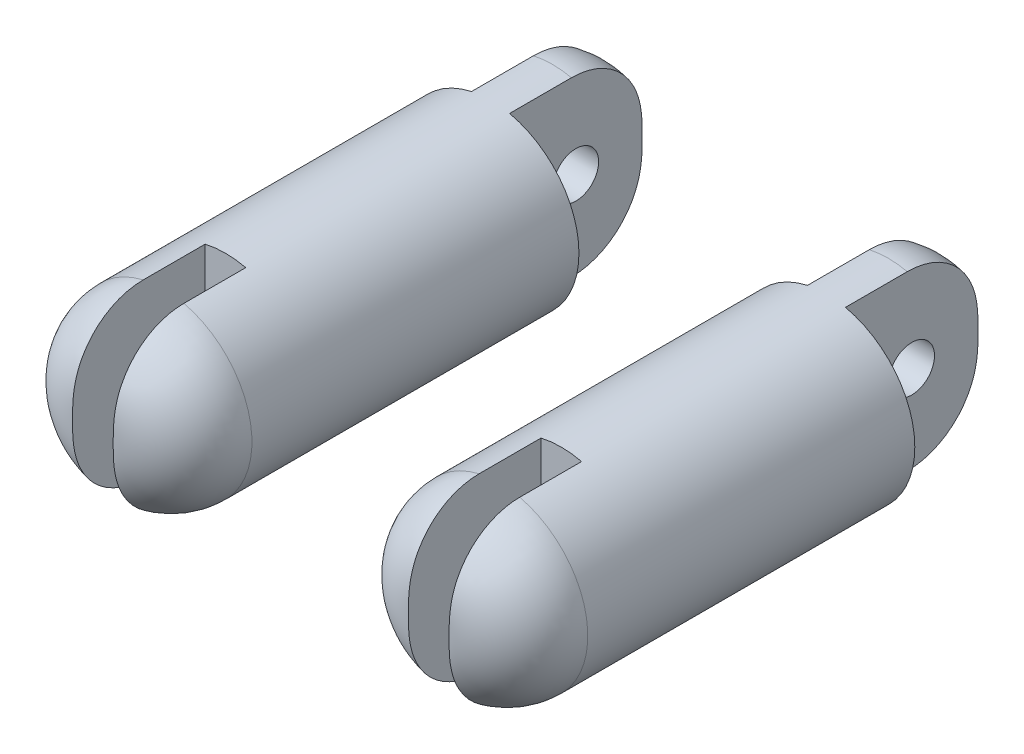
SolidWorks part; units mm, degrees
ref_plane "Front Plane" through (0, 0, 0) normal (0, 0, 1) x (1, 0, 0)
ref_plane "Top Plane" through (0, 0, 0) normal (0, 1, 0) x (1, 0, 0)
ref_plane "Right Plane" through (0, 0, 0) normal (1, 0, 0) x (0, 0, -1)
sketch "Sketch1" plane through (0, 0, 0) normal (0, 0, 1) x (1, 0, 0)
  circle A0 centre (147.5676, 0) radius 100
  circle A1 centre (-232.4324, 0) radius 100
  dimension "D1" = 200
  dimension "D2" = 200
  dimension "D3" = 380
extrude "Boss-Extrude1" add sketch "Sketch1" along normal blind 600
fillet "Fillet1" radius 80 1 edges at (-132.4324, 0, 600)
fillet "Fillet2" radius 80 1 edges at (247.5676, 0, 600)
ref_plane "Plane1" through (0, 0, 600) normal (0, 0, 1) x (1, 0, 0)
sketch "Sketch2" plane through (0, 0, 600) normal (0, 0, 1) x (1, 0, 0)
  line L0 (-232.4324, 100) -> (-232.4324, -100) construction
  line L2 (-255.4324, -115.931) -> (-209.4324, -115.931)
  line L3 (-255.4324, -115.931) -> (-255.4324, 115.931)
  line L4 (-255.4324, 115.931) -> (-209.4324, 115.931)
  line L5 (-209.4324, -115.931) -> (-209.4324, 115.931)
  line L6 (-255.4324, -115.931) -> (-209.4324, 115.931) construction
  line L7 (-255.4324, 115.931) -> (-209.4324, -115.931) construction
  line L8 (124.5676, -115.931) -> (170.5676, -115.931)
  line L9 (124.5676, -115.931) -> (124.5676, 115.931)
  line L10 (124.5676, 115.931) -> (170.5676, 115.931)
  line L11 (170.5676, -115.931) -> (170.5676, 115.931)
  line L12 (124.5676, -115.931) -> (170.5676, 115.931) construction
  line L13 (124.5676, 115.931) -> (170.5676, -115.931) construction
  circle A0 centre (-232.4324, 0) radius 100 construction
  point P4 (-232.4324, 0)
  point P9 (147.5676, 0)
  dimension "D1" = 46
  dimension "D2" = 46
extrude "Cut-Extrude1" cut sketch "Sketch2" against normal blind 150
ref_plane "Plane2" through (-132.4324, 0, 0) normal (1, 0, 0) x (0, 0, -1)
ref_plane "Plane3" through (-332.4324, 0, 0) normal (-1, 0, 0) x (0, 0, 1)
ref_plane "Plane4" through (-232.4324, 0, 0) normal (-1, 0, 0) x (0, 0, 1)
sketch "Sketch3" plane through (-232.4324, 0, 0) normal (1, 0, 0) x (0, 0, -1)
  line L0 (-599.9437, 0) -> (-449.9585, 0) construction
  circle A0 centre (-524.9511, 0) radius 20.1551
  spline S0 degree 3 poles (-520, -97.3191) (-521.4805, -97.3191) (-522.9639, -97.2769) (-525.1936, -97.1492) (-525.9376, -97.0959) (-527.427, -96.9676) (-528.1733, -96.8925) (-531.8854, -96.4646) (-534.8091, -95.9549) (-540.5675, -94.6119) (-543.4022, -93.7785) (-547.5872, -92.2845) (-548.971, -91.7458) (-551.0296, -90.8755) (-551.7129, -90.575) (-553.0738, -89.9531) (-553.751, -89.6318) (-557.1007, -87.9831) (-559.6824, -86.5222) (-564.6562, -83.3259) (-567.0482, -81.5904) (-570.4934, -78.7805) (-571.6179, -77.8093) (-573.8185, -75.7968) (-574.8973, -74.7523) (-578.024, -71.5486) (-579.9713, -69.3121) (-583.6015, -64.6453) (-585.2844, -62.215) (-587.6111, -58.4244) (-588.3537, -57.1367) (-589.7723, -54.5124) (-590.4495, -53.1729) (-593.6321, -46.4282) (-595.559, -40.8337) (-597.2787, -33.6194) (-597.5881, -32.1655) (-598.1409, -29.2364) (-598.3844, -27.759) (-599.0179, -23.3262) (-599.3114, -20.3634) (-599.7094, -14.4269) (-599.8145, -11.4531) (-599.9017, -6.9883) (-599.9192, -5.4993) (-599.9353, -3.2653) (-599.9389, -2.5205) (-599.9433, -1.0308) (-599.9441, -0.2845) (-599.9413, 3.4235) (-599.9216, 6.3892) (-599.7866, 12.3168) (-599.6678, 15.2785) (-599.3433, 19.7151) (-599.2109, 21.193) (-598.8885, 24.1464) (-598.6989, 25.6171) (-598.038, 30) (-597.4735, 32.8866) (-595.3686, 41.4291) (-593.4197, 46.9685) (-590.5235, 52.9997) (-590.1915, 53.6678) (-589.5119, 54.9896) (-588.4681, 56.9536) (-587.3514, 58.862) (-585.0218, 62.6054) (-583.3409, 65.0034) (-579.7234, 69.6043) (-577.787, 71.8073) (-574.6846, 74.961) (-573.6174, 75.987) (-571.9657, 77.4871) (-571.4061, 77.9811) (-570.2775, 78.9492) (-569.7076, 79.4241) (-566.8303, 81.7542) (-562.05, 85.196) (-556.9236, 88.077) (-552.9468, 90.0239) (-551.5991, 90.6372) (-549.5438, 91.5022) (-548.8519, 91.7819) (-547.464, 92.3198) (-546.7678, 92.5782) (-543.2757, 93.8183) (-537.6172, 95.4702) (-531.82, 96.4733) (-527.4194, 96.9788) (-525.9437, 97.1061) (-523.7166, 97.2339) (-522.9709, 97.2659) (-521.4834, 97.3085) (-520.741, 97.3191) (-520, 97.3191) knots 0 0 0 0 0.015625 0.015625 0.023437 0.023437 0.03125 0.03125 0.0625 0.0625 0.09375 0.09375 0.109375 0.109375 0.117187 0.117187 0.125 0.125 0.15625 0.15625 0.1875 0.1875 0.203125 0.203125 0.21875 0.21875 0.25 0.25 0.28125 0.28125 0.296875 0.296875 0.3125 0.3125 0.375 0.375 0.390625 0.390625 0.40625 0.40625 0.4375 0.4375 0.46875 0.46875 0.484375 0.484375 0.492187 0.492187 0.5 0.5 0.53125 0.53125 0.5625 0.5625 0.578125 0.578125 0.59375 0.59375 0.625 0.625 0.6875 0.6875 0.695312 0.695312 0.703125 0.71875 0.71875 0.75 0.75 0.78125 0.78125 0.796875 0.796875 0.804687 0.804687 0.8125 0.8125 0.84375 0.875 0.875 0.890625 0.890625 0.898438 0.898438 0.90625 0.90625 0.9375 0.96875 0.96875 0.984375 0.984375 0.992188 0.992188 1 1 1 1 construction
  point P3 (-448.2608, 0)
  point P6 (0, 0)
  point P7 (-610.9524, 0)
  point P8 (0, 0)
  point P9 (-599.9437, 0)
  point P12 (-449.9585, 0)
extrude "Boss-Extrude2" add sketch "Sketch3" along normal up to surface and the other way up to surface up to face at (-209.4324, 0.5625, 465.0151) other way up to face at (-255.4324, -0.5625, 465.0151)
sketch "Sketch4" plane through (0, 0, 0) normal (0, 0, -1) x (-1, 0, 0)
  line L1 (-169.0819, -97.6583) -> (-126.0533, -97.6583)
  line L2 (-169.0819, -97.6583) -> (-169.0819, 97.6583)
  line L3 (-169.0819, 97.6583) -> (-126.0533, 97.6583)
  line L4 (-126.0533, -97.6583) -> (-126.0533, 97.6583)
  line L5 (-169.0819, -97.6583) -> (-126.0533, 97.6583) construction
  line L6 (-169.0819, 97.6583) -> (-126.0533, -97.6583) construction
  line L7 (210.9181, -97.6583) -> (253.9467, -97.6583)
  line L8 (210.9181, -97.6583) -> (210.9181, 97.6583)
  line L9 (210.9181, 97.6583) -> (253.9467, 97.6583)
  line L10 (253.9467, -97.6583) -> (253.9467, 97.6583)
  line L11 (210.9181, -97.6583) -> (253.9467, 97.6583) construction
  line L12 (210.9181, 97.6583) -> (253.9467, -97.6583) construction
  circle A0 centre (-147.5676, 0) radius 100 construction
  circle A1 centre (232.4324, 0) radius 100 construction
  circle A2 centre (-147.5676, 0) radius 100
  circle A3 centre (232.4324, 0) radius 100
  point P0 (-147.5676, 0)
  point P8 (232.4324, 0)
  circle M1 centre (-147.5676, 0) radius 100
extrude "Cut-Extrude2" cut sketch "Sketch4" against normal blind 150 contours L10 A3 | L8 A3 | L4 M1 | L2 M1 region at (201.8508, 0, 0) region at (93.2844, 0, 0) region at (-178.1492, 0, 0) region at (-286.7156, 0, 0)
fillet "Fillet3" radius 80 1 edges at (147.5676, 100, 0)
fillet "Fillet4" radius 80 1 edges at (-232.4324, 100, 0)
sketch "Sketch5" plane through (169.0819, 0, 0) normal (1, 0, 0) x (0, 0, -1)
  line L0 (0, 0) -> (-150, 0) construction
  line L1 (-150, -97.6583) -> (-150, 97.6583) construction
  circle A0 centre (-75, 0) radius 25.7363
extrude "Cut-Extrude3" cut sketch "Sketch5" against normal blind 520
